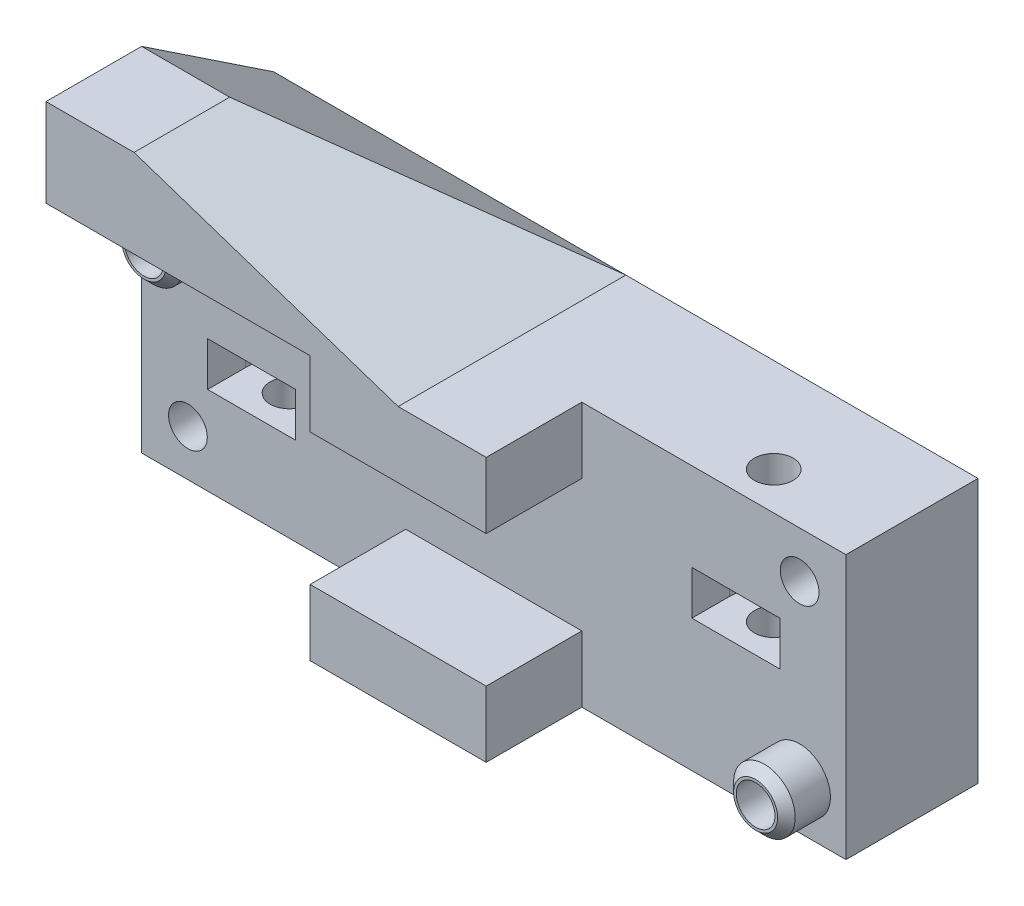
SolidWorks part; units mm, degrees
ref_plane "Front Plane" through (0, 0, 0) normal (0, 0, 1) x (1, 0, 0)
ref_plane "Top Plane" through (0, 0, 0) normal (0, 1, 0) x (1, 0, 0)
ref_plane "Right Plane" through (0, 0, 0) normal (1, 0, 0) x (0, 0, -1)
sketch "Sketch1" plane through (0, 0, 0) normal (0, 0, 1) x (1, 0, 0)
  line L1 (-25.4, 9.525) -> (25.4, 9.525)
  line L2 (-25.4, 9.525) -> (-25.4, -9.525)
  line L3 (-25.4, -9.525) -> (25.4, -9.525)
  line L4 (25.4, 9.525) -> (25.4, -9.525)
  line L5 (-25.4, 9.525) -> (25.4, -9.525) construction
  line L6 (-25.4, -9.525) -> (25.4, 9.525) construction
  point P0 (0, 0)
  dimension "D1" = 50.8
  dimension "D2" = 19.05
extrude "Boss-Extrude1" add sketch "Sketch1" along normal blind 9.525
sketch "Sketch11" plane through (0, 9.525, 0) normal (0, 1, 0) x (1, 0, 0)
  line L1 (-25.4, 0) -> (0, 0)
  line L2 (-25.4, 0) -> (-25.4, -16.4211)
  line L3 (-25.4, -16.4211) -> (0, -16.4211)
  line L4 (0, 0) -> (0, -16.4211)
  line L5 (-25.4, -25.9461) -> (-25.4, -16.4211) construction
  line L6 (12.6942, -16.4211) -> (0, -16.4211) construction
  dimension "D1" = 25.4
extrude "Boss-Extrude5" add sketch "Sketch11" along normal blind 6.35
sketch "Sketch2" plane through (0, 0, 9.525) normal (0, 0, 1) x (1, 0, 0)
  line L0 (-22.0599, -6.1849) -> (-22.0599, 6.1849) construction
  line L1 (-22.0599, 6.1849) -> (-25.4, 6.1849) construction
  line L2 (-25.4, 9.525) -> (-25.4, -9.525) construction
  line L3 (-22.0599, 6.1849) -> (-22.0599, 9.525) construction
  line L4 (25.4, 9.525) -> (0, 9.525) construction
  line L5 (0, -9.525) -> (0, 9.525) construction
  line L6 (25.4, 9.525) -> (0, 9.525) construction
  circle A0 centre (-22.0599, -6.1849) radius 1.397
  circle A1 centre (-22.0599, 6.1849) radius 1.397
  circle A2 centre (22.0599, -6.1849) radius 1.397
  circle A3 centre (22.0599, 6.1849) radius 1.397
  point P4 (-22.0599, 0)
  point P16 (0, 0)
  dimension "D1" = 2.794
  dimension "D2" = 2.794
  dimension "D3" = 12.3698
extrude "Cut-Extrude1" cut sketch "Sketch2" against normal through all
sketch "Sketch5" plane through (0, 9.525, 0) normal (0, 1, 0) x (1, 0, 0)
  line L0 (-25.4, -9.525) -> (-25.4, 0) construction
  line L1 (25.4, 0) -> (0, 0) construction
  line L2 (0, 0) -> (0, -9.525) construction
  line L4 (25.4, -9.525) -> (0, -9.525) construction
  circle A0 centre (-17.4625, -6.7945) radius 1.397
  circle A1 centre (17.4625, -6.7945) radius 1.397
  dimension "D1" = 7.9375
  dimension "D2" = 2.794
  dimension "D3" = 6.7945
extrude "Cut-Extrude3" cut sketch "Sketch5" against normal through all
sketch "Sketch3" plane through (0, 9.525, 0) normal (0, 1, 0) x (1, 0, 0)
  line L0 (-20.6375, -6.7945) -> (-20.6375, -9.525)
  line L1 (25.4, -9.525) -> (0, -9.525) construction
  line L2 (-14.2875, -6.7945) -> (-14.2875, -9.525)
  line L3 (-14.2875, -9.525) -> (-20.6375, -9.525)
  arc A0 (-14.2875, -6.7945) -> (-20.6375, -6.7945) centre (-17.4625, -6.7945) ccw
  circle A1 centre (-17.4625, -6.7945) radius 1.397 construction
  dimension "D1" = 3.175
extrude "Cut-Extrude2" cut sketch "Sketch3" against normal blind 3.175 from offset 9.525 offset against normal yes
sketch "Sketch6" plane through (0, 9.525, 0) normal (0, 1, 0) x (1, 0, 0)
  line L0 (14.2875, -6.7945) -> (14.2875, -9.525)
  line L1 (25.4, -9.525) -> (0, -9.525) construction
  line L2 (20.6375, -6.7945) -> (20.6375, -9.525)
  line L3 (14.2875, -9.525) -> (20.6375, -9.525)
  arc A0 (20.6375, -6.7945) -> (14.2875, -6.7945) centre (17.4625, -6.7945) ccw
  dimension "D1" = 6.35
extrude "Cut-Extrude4" cut sketch "Sketch6" against normal blind 3.175 from offset 6.35 offset against normal yes
sketch "Sketch7" plane through (0, 0, 9.525) normal (0, 0, 1) x (1, 0, 0)
  circle A0 centre (-22.0599, 6.1849) radius 2.2225
  circle A1 centre (-22.0599, 6.1849) radius 1.397
  circle A2 centre (22.0599, -6.1849) radius 2.2225
  circle A3 centre (22.0599, -6.1849) radius 1.397
  circle A5 centre (-22.0599, 6.1849) radius 1.397 construction
  circle A6 centre (22.0599, -6.1849) radius 1.397 construction
  dimension "D1" = 4.445
extrude "Boss-Extrude2" add sketch "Sketch7" along normal blind 3.175
chamfer "Chamfer1" distance 0.635 angle 45 2 edges at (-19.8374, 6.1849, 12.7) (24.2824, -6.1849, 12.7)
sketch "Sketch10" plane through (0, 0, 9.525) normal (0, 0, 1) x (1, 0, 0)
  line L0 (25.4, 9.525) -> (0, 9.525) construction
  line L1 (-6.35, 9.525) -> (6.35, 9.525)
  line L2 (-6.35, 9.525) -> (-6.35, 4.7625)
  line L3 (-6.35, 4.7625) -> (6.35, 4.7625)
  line L4 (6.35, 9.525) -> (6.35, 4.7625)
  line L5 (-25.4, -9.525) -> (25.4, -9.525) construction
  line L6 (-6.35, -9.525) -> (6.35, -9.525)
  line L7 (-6.35, -9.525) -> (-6.35, -4.7625)
  line L8 (-6.35, -4.7625) -> (6.35, -4.7625)
  line L9 (6.35, -9.525) -> (6.35, -4.7625)
  point P6 (0, 4.7625)
  point P14 (0, -4.7625)
  dimension "D1" = 12.7
  dimension "D2" = 4.7625
  dimension "D3" = 4.7625
  dimension "D4" = 12.7
extrude "Boss-Extrude4" add sketch "Sketch10" along normal blind 6.8961
chamfer "Chamfer2" distance 6.35 distance2 9.525 1 edges at (-12.7, 15.875, 0) first distance on face at (-20.6629, 6.1849, 0)
chamfer "Chamfer3" distance 6.35 distance2 19.05 1 edges at (0, 15.875, 12.9731) first distance on face at (0, 12.7, 10.5918)
